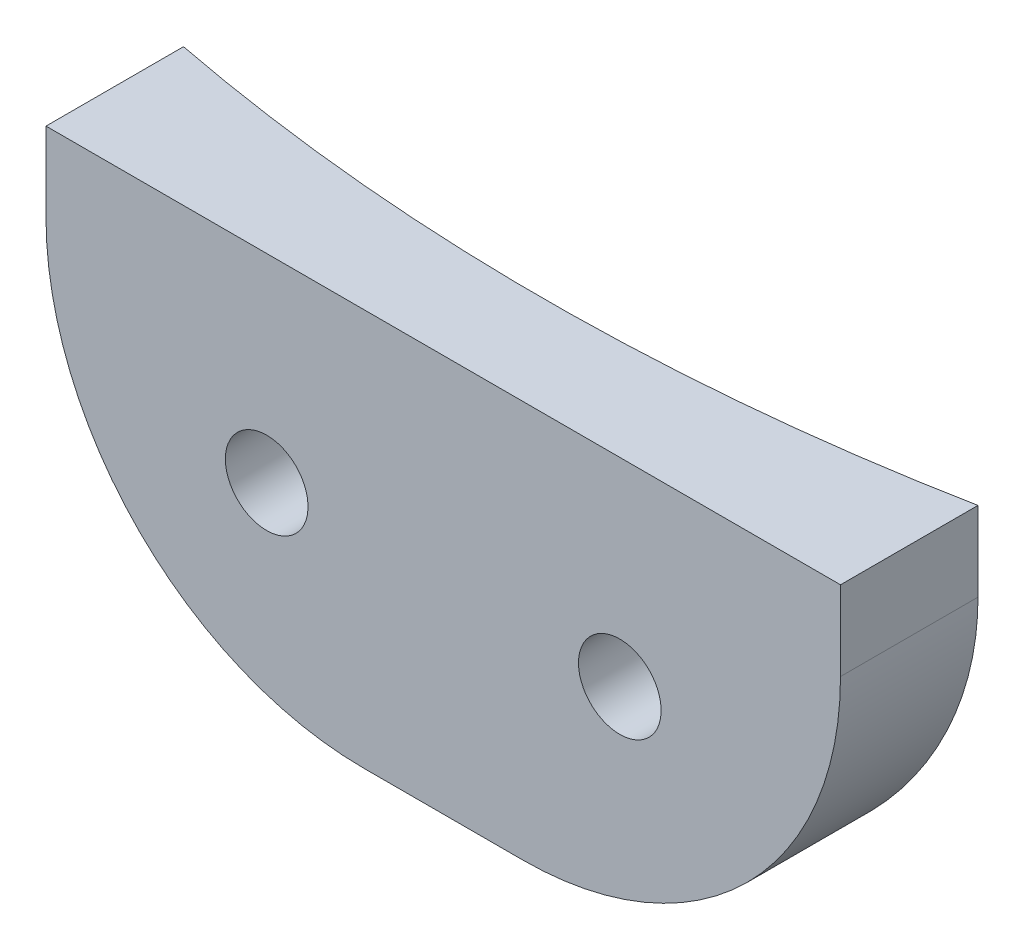
SolidWorks part; units mm, degrees
material "6061 Alloy"
ref_plane "Front Plane" through (0, 0, 0) normal (0, 0, 1) x (1, 0, 0)
ref_plane "Top Plane" through (0, 0, 0) normal (0, 1, 0) x (1, 0, 0)
ref_plane "Right Plane" through (0, 0, 0) normal (1, 0, 0) x (0, 0, -1)
sketch "Sketch1" plane through (0, 0, 0) normal (0, 1, 0) x (1, 0, 0)
  line L0 (-12.7, -65.4543) -> (-12.7, -68.6858)
  line L1 (12.7, -65.4543) -> (12.7, -68.6858)
  line L2 (-12.7, -69.85) -> (12.7, -69.85)
  line L3 (-12.7, -68.6858) -> (-12.7, -69.85)
  line L4 (12.7, -68.6858) -> (12.7, -69.85)
  circle A0 centre (0, 0) radius 66.675
  circle A1 centre (0, 0) radius 69.85
  dimension "D1" = 133.35
  dimension "D3" = 12.7
  dimension "D4" = 12.7
  dimension "D2" = 3.175
extrude "Boss-Extrude1" add sketch "Sketch1" along normal blind 12.7 contours L0 A1 L1 A0 | A1 L3 L2 | A1 L2 L4 region at (0, 0, 67.8645) region at (-9.5303, 0, 69.5012) region at (9.5303, 0, 69.5012)
sketch "Sketch2" plane through (0, 0, 0) normal (0, 0, 1) x (1, 0, 0)
  line L0 (0, 12.7) -> (0, 0) construction
  line L5 (-12.7, 0) -> (12.7, 0)
  line L6 (12.7, 0) -> (12.7, 12.7)
  line L7 (12.7, 12.7) -> (-12.7, 12.7)
  line L12 (-12.7, 12.7) -> (-12.7, 0)
  line L13 (-12.7, 0) -> (12.7, 0)
  line L14 (12.7, 0) -> (12.7, 12.7)
  line L15 (12.7, 12.7) -> (-12.7, 12.7)
  line L16 (-12.7, 12.7) -> (-12.7, 0)
  circle A0 centre (-5.6444, 6.35) radius 1.3208
  dimension "D6" = 2.6416
  dimension "D5" = 5.6444
  dimension "D2" = 6.35
extrude "Cut-Extrude1" cut sketch "Sketch2" along normal up to surface (69.85 mm away) contours A0 up to face at (0, 6.35, 69.85)
mirror "Mirror1" about plane through (0, 0, 0) normal (1, 0, 0) of "Cut-Extrude1"
sketch "Sketch3" plane through (0, 0, 0) normal (0, 0, 1) x (1, 0, 0)
  line L0 (-12.7, 12.7) -> (-12.7, 0)
  line L6 (-12.7, 0) -> (0, 0)
  line L7 (12.7, 12.7) -> (12.7, 0)
  line L8 (-2.54, 0) -> (2.54, 0)
  line L9 (12.7, 10.16) -> (12.7, 12.7)
  line L10 (12.7, 12.7) -> (-12.7, 12.7)
  line L11 (-12.7, 12.7) -> (-12.7, 10.16)
  line L12 (12.7, 0) -> (2.54, 0)
  arc A0 (2.54, 0) -> (12.7, 10.16) centre (2.54, 10.16) ccw
  arc A1 (-2.54, 0) -> (-12.7, 10.16) centre (-2.54, 10.16) cw
  dimension "D2" = 10.16
  dimension "D6" = 2.54
  dimension "D1" = 12.7
  dimension "D3" = 12.7
  dimension "D4" = 2.54
  dimension "D5" = 2.54
  dimension "D7" = 2.54
  dimension "D8" = 2.54
  dimension "D9" = 10.16
extrude "Cut-Extrude2" cut sketch "Sketch3" along normal up to surface (69.85 mm away) contours L6 A1 L0 | A0 L12 L7 region at (-10.4306, 2.2694, 0) region at (10.4306, 2.2694, 0) up to face at (4.3236, 6.35, 69.85)
equation "\"Middle Coupler Inner Daimeter\"= 4.75in"
equation "\"Middle Coupler  Wall Thickness\" = 0.25in"
equation "\"Middle Coupler Bottom Thickness\"= 0.2in"
equation "\"Bearing Rail Offset\"= 0.45in"
equation "\"3-56 UNF Tap\"= 0.089in"
equation "\"3-56 UNF Clearance\"= 0.104in"
equation "\"Ball Bearing Distance\"= 0.03in"
equation "\"TCA Outer Diameter\" = 6.625in"
equation "\"D1@Sketch1\"=\"Middle Coupler Inner Daimeter\"+0.5"
equation "\"D2@Sketch1\"=1/8"
equation "\"D3@Sketch1\"=0.5"
equation "\"D4@Sketch1\"=\"D3@Sketch1\""
equation "\"D6@Sketch2\"=\"3-48 Clearance\""
equation "\"Interstage Aeroframe Wall Thickness\" = 0.072in"
equation "\"Compression Spring OD\"= 0.42in"
equation "\"10-24 Tap\"= 0.157in"
equation "\"10-24 Clearance\"= 0.196in"
equation "\"Lower Stage Fuselage Wall Thickness\" = 0.25in"
equation "\"6-32 Tap\" = 0.107in"
equation "\"1/4-20 Tap\" = 0.201in"
equation "\"3-48 Tap\"= 0.079in"
equation "\"3-48 Clearance\" = 0.104in"
equation "\"6-32 Clearance\" = 0.144"
equation "\"12-24 Tap\" = 0.177in"
